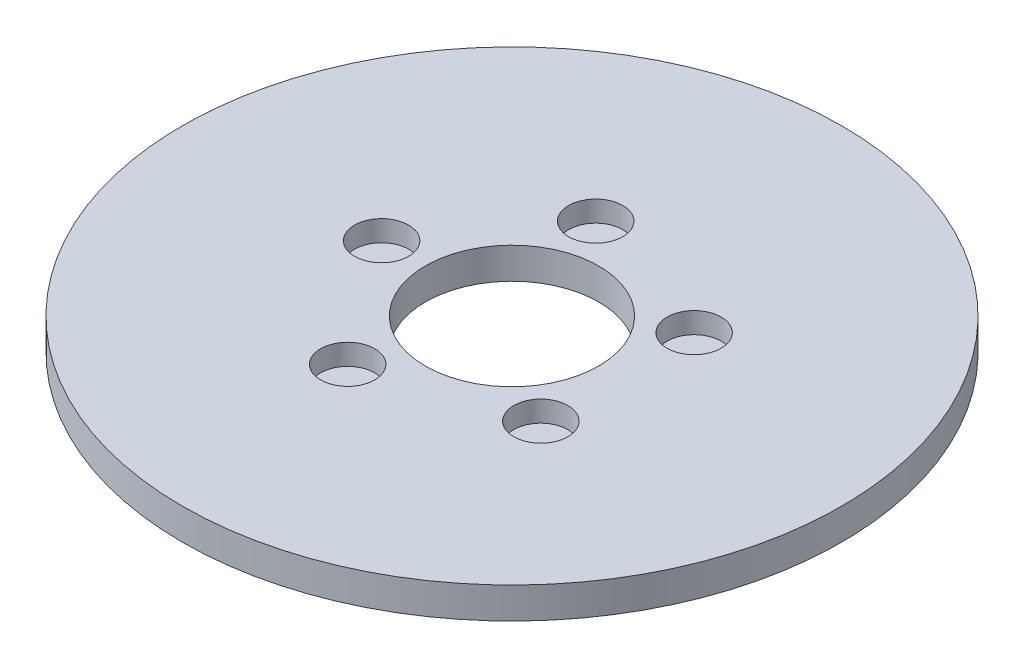
SolidWorks part; units mm, degrees
ref_plane "Front Plane" through (0, 0, 0) normal (0, 0, 1) x (1, 0, 0)
ref_plane "Top Plane" through (0, 0, 0) normal (0, 1, 0) x (1, 0, 0)
ref_plane "Right Plane" through (0, 0, 0) normal (1, 0, 0) x (0, 0, -1)
sketch "Sketch1" plane through (0, 0, 0) normal (0, 1, 0) x (1, 0, 0)
  circle A0 centre (0, 0) radius 95
  dimension "FLANGE_OD" = 190
extrude "Boss-Extrude1" add sketch "Sketch1" along normal blind 9
sketch "Sketch2" plane through (0, 0, 0) normal (0, 1, 0) x (1, 0, 0)
  circle A0 centre (0, 0) radius 25
  dimension "BORE_D" = 50
extrude "Cut-Extrude1" cut sketch "Sketch2" along normal through all
sketch "Sketch3" plane through (0, 9, 0) normal (0, 1, 0) x (1, 0, 0)
  circle A0 centre (0, 0) radius 37.588 construction
  circle A1 centre (-37.588, 0) radius 7.798
  dimension "BOLT_D" = 15.5959
  dimension "BOLT_PCD" = 75.1761
extrude "Cut-Extrude2" cut sketch "Sketch3" against normal blind 6.0253
pattern_circular "CirPattern1" count 5 over 360 about axis through (0, 0, 0) along (0, 1, 0) of "Cut-Extrude2"
